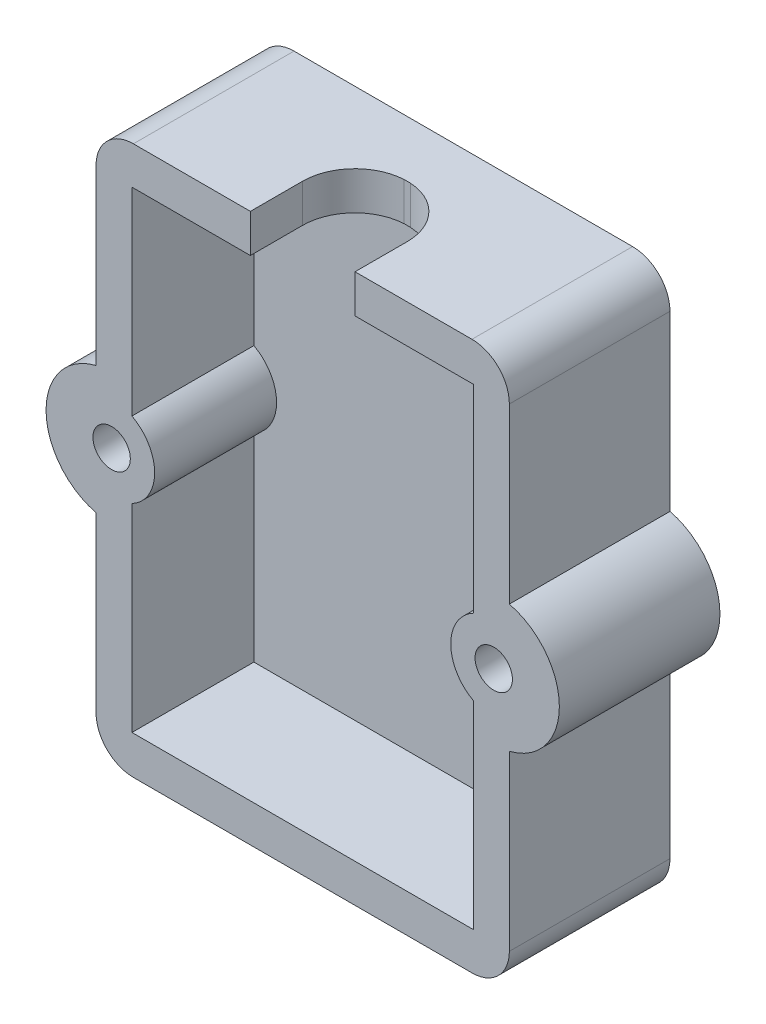
SolidWorks part; units mm, degrees
ref_plane "Front Plane" through (0, 0, 0) normal (0, 0, 1) x (1, 0, 0)
ref_plane "Top Plane" through (0, 0, 0) normal (0, 1, 0) x (1, 0, 0)
ref_plane "Right Plane" through (0, 0, 0) normal (1, 0, 0) x (0, 0, -1)
sketch "Sketch1" plane through (0, 0, 0) normal (0, 0, 1) x (1, 0, 0)
  line L0 (0, 0) -> (0, 25.5) construction
  line L1 (-15, 25.5) -> (15, 25.5) construction
  line L2 (-10.225, 13.5) -> (0, 13.5) construction
  line L3 (0, 13.5) -> (10.225, 13.5) construction
  line L4 (-11.06, 0.8164) -> (-11.06, 10.0908)
  line L9 (0, 25.1336) -> (0, -0.2336) construction
  line L10 (-9.06, 13.5) -> (9.06, 13.5) construction
  line L11 (-9.06, 28.1836) -> (9.06, 28.1836)
  line L12 (11.06, 0.8164) -> (11.06, 10.0908)
  line L13 (-9.06, -1.1836) -> (9.06, -1.1836)
  line L18 (-11.06, 16.9092) -> (-11.06, 26.1836)
  line L20 (11.06, 16.9092) -> (11.06, 26.1836)
  arc A2 (11.06, 16.9092) -> (11.06, 10.0908) centre (10.225, 13.5) cw
  arc A3 (-11.06, 16.9092) -> (-11.06, 10.0908) centre (-10.225, 13.5) ccw
  arc A4 (-11.06, 0.8164) -> (-9.06, -1.1836) centre (-9.06, 0.8164) ccw
  arc A5 (11.06, 0.8164) -> (9.06, -1.1836) centre (9.06, 0.8164) cw
  arc A6 (9.06, 28.1836) -> (11.06, 26.1836) centre (9.06, 26.1836) cw
  arc A8 (-11.06, 26.1836) -> (-9.06, 28.1836) centre (-9.06, 26.1836) cw
  point P11 (-13.735, 13.5)
  dimension "D1" = 2
  dimension "D2" = 6.8185
  dimension "D3" = 29.3672
extrude "Boss-Extrude2" add sketch "Sketch1" along normal blind 8.595 contours L11 A6 L20 A2 L12 A5 L13 A4 L4 A3 L18 A8
sketch "Sketch2" plane through (0, 0, 8.595) normal (0, 0, 1) x (1, 0, 0)
  line L6 (0, -1.1836) -> (0, 28.1836) construction
  line L7 (-9.06, -1.1836) -> (9.06, -1.1836) construction
  line L8 (-9.06, 28.1836) -> (9.06, 28.1836) construction
  line L9 (13.735, 13.5) -> (-13.735, 13.5) construction
  line L10 (0, -0.2133) -> (0, 25.2203) construction
  line L11 (-10.5637, 13.5) -> (9.8863, 13.5) construction
  line L12 (-9.1375, 15.5286) -> (-9.1375, 26.1364)
  line L13 (-9.1375, 0.8614) -> (9.1375, 0.8614)
  line L14 (-9.1375, 0.8614) -> (-9.1375, 11.4714)
  line L15 (-9.1375, 26.1364) -> (9.1375, 26.1364)
  line L16 (9.1375, 0.8614) -> (9.1375, 11.4714)
  line L17 (0, 26.1364) -> (0, 0.8614) construction
  line L18 (-9.075, 13.5) -> (9.075, 13.5) construction
  line L19 (9.1375, 15.5286) -> (9.1375, 26.1364)
  line L21 (-9.06, -1.1836) -> (9.06, -1.1836) construction
  arc A2 (11.06, 10.0908) -> (11.06, 16.9092) centre (10.225, 13.5) ccw construction
  arc A3 (-11.06, 16.9092) -> (-11.06, 10.0908) centre (-10.225, 13.5) ccw construction
  arc A4 (-9.1375, 11.4714) -> (-9.1375, 15.5286) centre (-10.225, 13.5) ccw
  arc A5 (9.1375, 11.4714) -> (9.1375, 15.5286) centre (10.225, 13.5) cw
  point P6 (0, 13.5)
  dimension "D1" = 25.275
  dimension "D2" = 18.275
  dimension "D4" = 2.045
sketch "Sketch5" plane through (0, 0, 8.595) normal (0, 0, 1) x (1, 0, 0)
  line L0 (0, 28.1836) -> (0, -1.1836) construction
  line L1 (-11.06, 0.8164) -> (-11.06, 10.0908) construction
  line L2 (-9.06, -1.1836) -> (9.06, -1.1836) construction
  circle A0 centre (-10.225, 13.5) radius 1
  circle A1 centre (10.225, 13.5) radius 1
  point P5 (0, 0)
  dimension "D1" = 20.12
  dimension "D3" = 2
  dimension "D2" = 11.2744
  dimension "D4" = 0.835
  dimension "D5" = 14.6836
extrude "Cut-Extrude3" cut sketch "Sketch5" against normal up to next
extrude "Cut-Extrude4" cut sketch "Sketch2" against normal blind 6.525
sketch "Sketch3" plane through (0, 28.1836, 0) normal (0, 1, 0) x (1, 0, 0)
  line L0 (0, 0) -> (0, -8.595) construction
  line L1 (-9.06, -8.595) -> (9.06, -8.595) construction
  line L2 (11.06, -4.2975) -> (-11.06, -4.2975) construction
  line L3 (11.06, -8.595) -> (11.06, 0) construction
  line L4 (-11.06, -8.595) -> (-11.06, 0) construction
  line L5 (-9.06, 0) -> (9.06, 0) construction
  line L7 (-0.1673, -3.005) -> (0.1673, -3.005)
  line L8 (-2.8, -5.8) -> (-2.8, -8.595)
  line L9 (-2.8, -8.595) -> (2.8, -8.595)
  line L10 (2.8, -5.8) -> (2.8, -8.595)
  line L11 (0, -8.595) -> (0, -3.005) construction
  line L12 (-2.8, -5.8) -> (2.8, -5.8) construction
  arc A0 (2.8, -5.8) -> (-2.8, -5.8) centre (0, -5.8) ccw
  arc A1 (-0.1673, -8.595) -> (0.1673, -8.595) centre (0, -5.8) ccw
  line M4 (-9.06, -8.595) -> (9.06, -8.595)
  dimension "D1" = 5.8
extrude "Cut-Extrude2" cut sketch "Sketch3" against normal up to next contours L10 A0 L7 L8 L9 M4 region at (0, 28.1836, 6.059)
